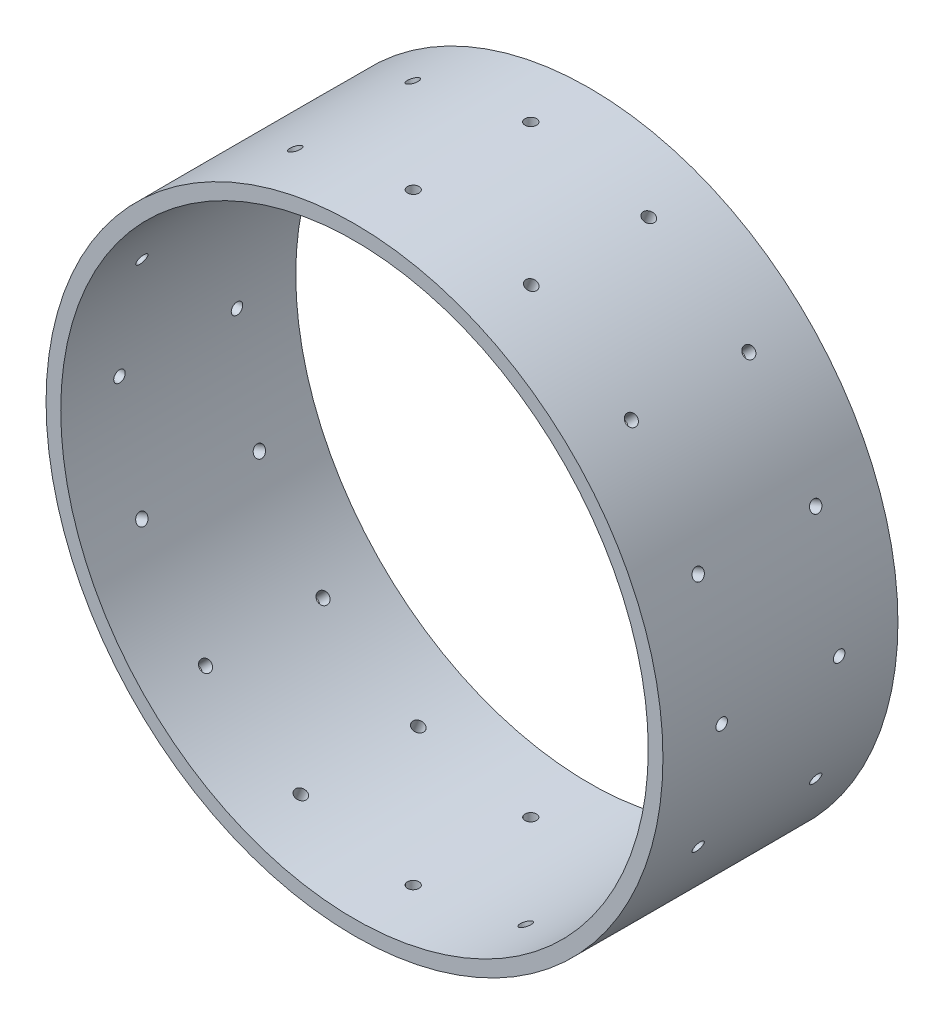
SolidWorks part; units mm, degrees
material "6061-T6 (SS)"
ref_plane "Front Plane" through (0, 0, 0) normal (0, 0, 1) x (1, 0, 0)
ref_plane "Top Plane" through (0, 0, 0) normal (0, 1, 0) x (1, 0, 0)
ref_plane "Right Plane" through (0, 0, 0) normal (1, 0, 0) x (0, 0, -1)
sketch "Sketch1" plane through (0, 0, 0) normal (0, 0, 1) x (1, 0, 0)
  circle A0 centre (0, 0) radius 63.5
  circle A1 centre (0, 0) radius 66.675
extrude "Extrude1" add sketch "Sketch1" along normal blind 50.8
ref_plane "Plane1" through (0, 0, 12.7) normal (0, 0, -1) x (-1, 0, 0)
sketch "Sketch2" plane through (0, 0, 12.7) normal (0, 0, -1) x (-1, 0, 0)
  line L0 (0, 0) -> (0, 66.675) construction
  circle A0 centre (0, 0) radius 66.675 construction
ref_plane "Plane4" through (0, 66.675, 12.7) normal (0, 1, 0) x (-1, 0, 0)
sketch "Sketch7" plane through (0, 66.675, 12.7) normal (0, 1, 0) x (-1, 0, 0)
  line L0 (0, 0) -> (0, 25.4) construction
hole_wizard "#40 (0.098) Diameter Hole2" positions "Sketch9" profile "Sketch8" hole size "#40" standard "Ansi Inch"
sketch "Sketch9" plane through (0, 66.675, 12.7) normal (0, 1, 0) x (-1, 0, 0)
  point P1 (0, 0)
  point P4 (0, 25.4)
sketch "Sketch8" plane through (0, 66.675, 12.7) normal (1, 0, 0) x (0, 0, 1)
  line L0 (0, 0) -> (0, 13.4478)
  line L1 (0, 13.4478) -> (1.2446, 12.7)
  line L2 (1.2446, 12.7) -> (1.2446, 0)
  line L5 (1.2446, 0) -> (0, 0)
  line L10 (0, 13.4478) -> (-1.2446, 12.7) construction
  line L11 (0, -6.35) -> (0, 107.95) construction
  dimension "Hole Dia." = 2.4892
  dimension "Hole Depth" = 12.7
  dimension "Drill Angle" = 118
pattern_circular "CirPattern1" count 16 over 360 about axis through (0, 0, 50.8) along (0, 0, -1) of "#40 (0.098) Diameter Hole2"
